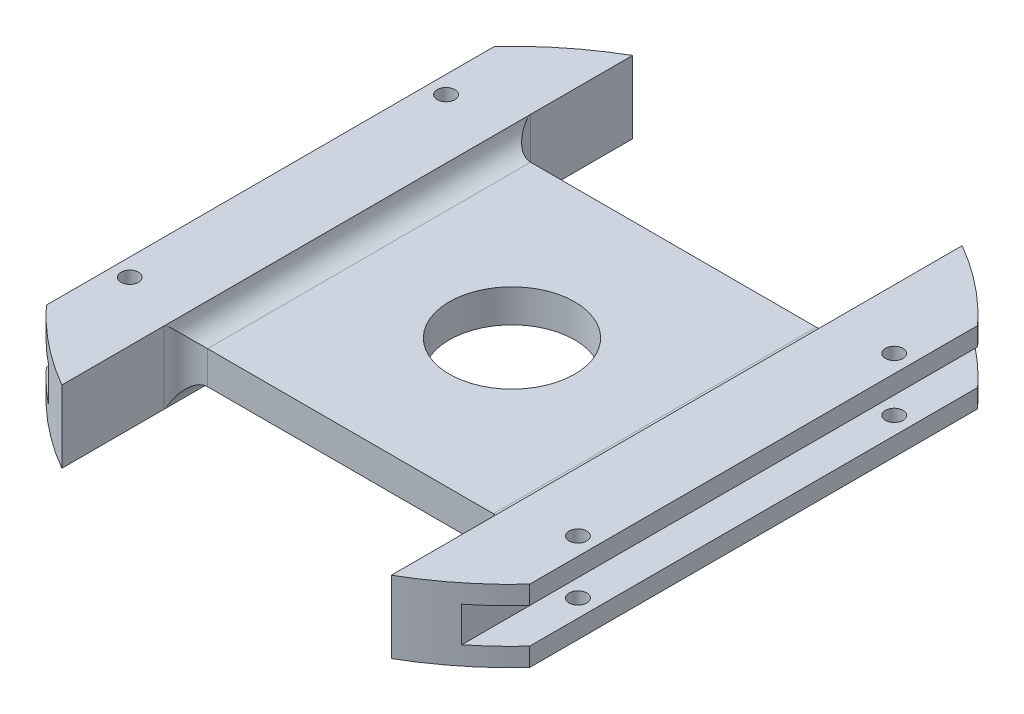
SolidWorks part; units mm, degrees
ref_plane "Alzado" through (0, 0, 0) normal (0, 0, 1) x (1, 0, 0)
ref_plane "Planta" through (0, 0, 0) normal (0, 1, 0) x (1, 0, 0)
ref_plane "Vista lateral" through (0, 0, 0) normal (1, 0, 0) x (0, 0, -1)
sketch "Croquis3" plane through (0, 0, 0) normal (0, 0, 1) x (1, 0, 0)
  line L0 (-75, 0) -> (75, 0) construction
  line L1 (0, 0) -> (0, 16.43) construction
  line L7 (-55, 0) -> (-37.5, 0)
  line L8 (-55, 0) -> (-55, 6.5)
  line L9 (-37.5, 4.465) -> (0, 4.465)
  line L14 (0, 8.215) -> (65.4059, 8.215) construction
  line L19 (-55, 16.43) -> (-55, 6.5)
  line L20 (-55, 16.43) -> (-37.5, 16.43)
  line L22 (-37.5, 11.965) -> (0, 11.965)
  line L23 (-37.5, 4.465) -> (-37.5, 0)
  line L24 (-55, 16.43) -> (-37.5, 16.43)
  line L25 (-55, 16.43) -> (-55, 0)
  line L26 (-55, 0) -> (-37.5, 0)
  line L27 (-37.5, 16.43) -> (-37.5, 11.965)
  line L28 (37.5, 16.43) -> (37.5, 11.965)
  line L29 (55, 0) -> (37.5, 0)
  line L30 (55, 16.43) -> (55, 0)
  line L31 (55, 16.43) -> (37.5, 16.43)
  line L32 (37.5, 4.465) -> (37.5, 0)
  line L33 (37.5, 11.965) -> (0, 11.965)
  line L34 (55, 16.43) -> (37.5, 16.43)
  line L35 (55, 16.43) -> (55, 6.5)
  line L36 (37.5, 4.465) -> (0, 4.465)
  line L37 (55, 0) -> (55, 6.5)
  line L38 (55, 0) -> (37.5, 0)
  point P4 (0, 0)
  point P28 (0, 0)
  dimension "D1" = 150
  dimension "D2" = 16.43
  dimension "D3" = 20
  dimension "D4" = 4.465
  dimension "D5" = 7.5
  dimension "D6" = 37.5
extrude "Saliente-Extruir1" add sketch "Croquis3" along normal mid plane 200 contours L36 L32 L29 L30 L31 L28 L33 L22 L27 L20 L19 L8 L7 L23 L9 region at (0, 8.215, 0)
sketch "Croquis4" plane through (0, 0, 0) normal (0, 1, 0) x (1, 0, 0)
  line L0 (37.5, -100) -> (37.5, 100) construction
  line L1 (-37.5, 77.7125) -> (37.5, 77.7125)
  line L2 (-37.5, 77.7125) -> (-37.5, 36.7521)
  line L3 (-37.5, 36.7521) -> (37.5, 36.7521)
  line L4 (37.5, 77.7125) -> (37.5, 36.7521)
  line L5 (-37.5, 77.7125) -> (37.5, 36.7521) construction
  line L6 (-37.5, 36.7521) -> (37.5, 77.7125) construction
  line L7 (0, 0) -> (71.2598, 0) construction
  line L8 (-37.5, -36.7521) -> (37.5, -77.7125) construction
  line L9 (-37.5, -77.7125) -> (37.5, -36.7521) construction
  line L10 (37.5, -77.7125) -> (37.5, -36.7521)
  line L11 (-37.5, -36.7521) -> (37.5, -36.7521)
  line L12 (-37.5, -77.7125) -> (-37.5, -36.7521)
  line L13 (-37.5, -77.7125) -> (37.5, -77.7125)
  circle A0 centre (0, 0) radius 75
  point P3 (0, 57.2323)
  point P15 (0, -57.2323)
  dimension "D1" = 150
extrude "Cortar-Extruir1" cut sketch "Croquis4" along normal through all both and the other way through all flip side to cut contours L10 A0 L4 L3 L2 L12 L11 | L4 A0 L2 L3 | L12 A0 L10 L11 region at (0, 0, -54.3745) region at (0, 0, 0) region at (0, 0, 54.3745)
extrude "Cortar-Extruir2" cut sketch "Croquis4<3>" against normal through all both and the other way through all contours L4 A0 L2 L3 | L12 A0 L10 L11 region at (0, 0, -54.3745) region at (0, 0, 54.3745)
sketch "Croquis4<3>" plane through (0, 0, 0) normal (0, 1, 0) x (1, 0, 0) same geometry as "Croquis4"
sketch "Croquis5" plane through (0, 11.965, 0) normal (0, 1, 0) x (1, 0, 0)
  circle A0 centre (0, 0) radius 14.27
  dimension "D1" = 28.54
extrude "Cortar-Extruir3" cut sketch "Croquis5" against normal through all both and the other way through all
fillet "Redondeo1" radius 5 8 edges at (37.5, 8.215, 36.7521) (-37.5, 8.215, -36.7521) (37.5, 8.215, -36.7521) (-37.5, 8.215, 36.7521) (37.5, 11.965, 0) (-37.5, 4.465, 0) (37.5, 4.465, 0) (-37.5, 11.965, 0)
sketch "Croquis7" plane through (0, 0, 0) normal (0, 0, 1) x (1, 0, 0)
  line L0 (-55, 0) -> (-55, 16.43) construction
  line L5 (0, 0) -> (0, 35.6388) construction
  line L6 (-55, 12.215) -> (-47, 12.215)
  line L7 (-55, 12.215) -> (-55, 4.215)
  line L8 (-55, 4.215) -> (-47, 4.215)
  line L9 (-47, 12.215) -> (-47, 4.215)
  line L10 (47, 12.215) -> (47, 4.215)
  line L11 (55, 4.215) -> (47, 4.215)
  line L12 (55, 12.215) -> (55, 4.215)
  line L13 (55, 12.215) -> (47, 12.215)
  point P4 (-55, 8.215)
  dimension "D1" = 8
  dimension "D2" = 8
extrude "Cortar-Extruir4" cut sketch "Croquis7" against normal through all both and the other way through all
sketch "Croquis8" plane through (0, 4.215, 0) normal (0, 1, 0) x (1, 0, 0)
  line L0 (-55, 50.9902) -> (-55, -50.9902) construction
  line L1 (0, 0) -> (0, 58.0522) construction
  circle A0 centre (-51, 35.9902) radius 2
  circle A1 centre (-51, -35.9902) radius 2
  circle A2 centre (51, -35.9902) radius 2
  circle A3 centre (51, 35.9902) radius 2
  dimension "D1" = 4
  dimension "D2" = 4
  dimension "D3" = 15
  dimension "D4" = 15
extrude "Cortar-Extruir5" cut sketch "Croquis8" against normal through all both and the other way through all
